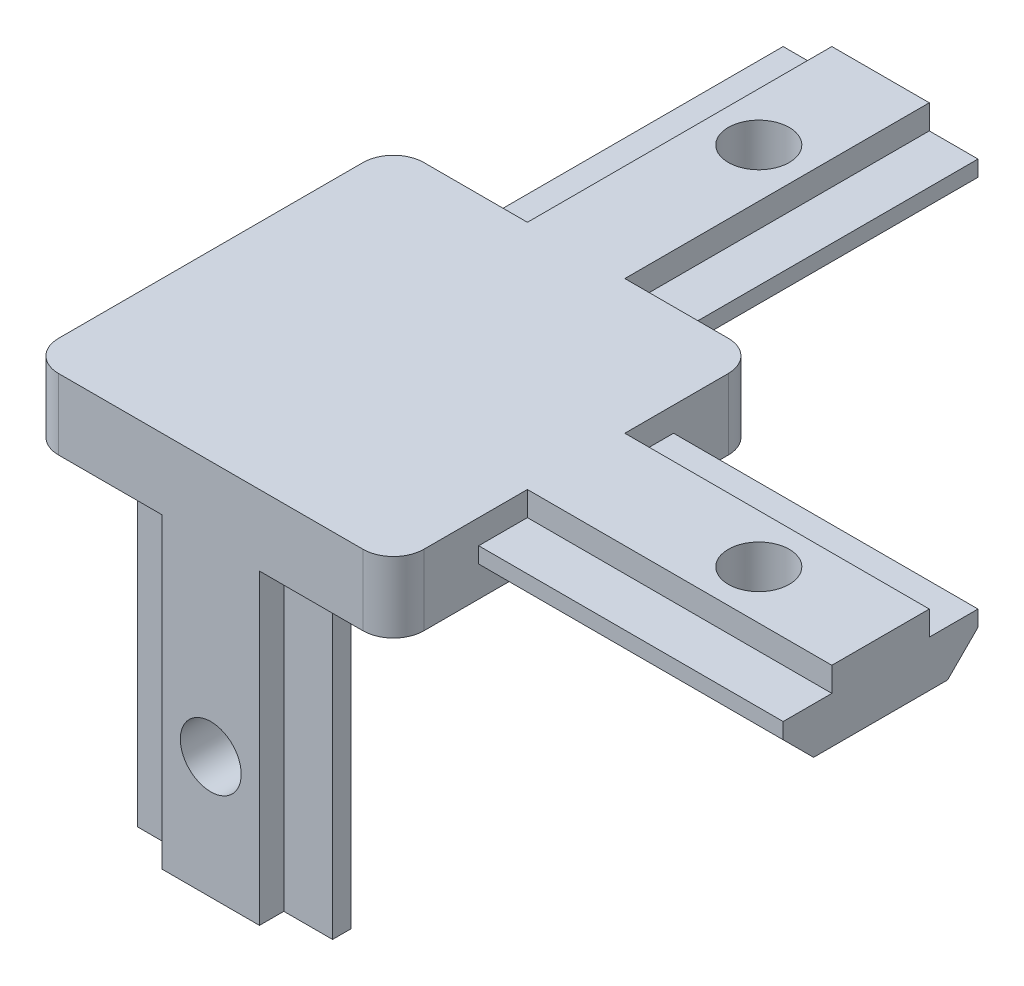
SolidWorks part; units mm, degrees
material "6063-T5"
ref_plane "前视基准面" through (0, 0, 0) normal (0, 0, 1) x (1, 0, 0)
ref_plane "上视基准面" through (0, 0, 0) normal (0, 1, 0) x (1, 0, 0)
ref_plane "右视基准面" through (0, 0, 0) normal (1, 0, 0) x (0, 0, -1)
sketch "草图1" plane through (0, 0, 0) normal (0, 1, 0) x (1, 0, 0)
  line L1 (-15, 15) -> (15, 15)
  line L2 (-15, 15) -> (-15, -15)
  line L3 (-15, -15) -> (15, -15)
  line L4 (15, 15) -> (15, -15)
  line L5 (-15, 15) -> (15, -15) construction
  line L6 (-15, -15) -> (15, 15) construction
  point P0 (0, 0)
  dimension "D1" = 30
  dimension "D2" = 30
extrude "凸台-拉伸1" add sketch "草图1" along normal blind 5.8
sketch "草图2" plane through (0, 0, 0) normal (0, -1, 0) x (-1, 0, 0)
  line L0 (0, 0) -> (0, -15) construction
  line L1 (15, -15) -> (-15, -15) construction
  line L2 (4, -15) -> (4, -13)
  line L3 (4, -13) -> (8, -13)
  line L4 (8, -13) -> (8, -11.5)
  line L5 (5.5, -9) -> (-5.5, -9)
  line L6 (8, -11.5) -> (5.5, -9)
  line L7 (4, -15) -> (-4, -15)
  line L8 (-8, -11.5) -> (-5.5, -9)
  line L9 (-8, -13) -> (-8, -11.5)
  line L10 (-4, -13) -> (-8, -13)
  line L11 (-4, -15) -> (-4, -13)
  line L12 (0, 0) -> (15, -15) construction
  line L13 (15, 4) -> (13, 4)
  line L14 (13, 4) -> (13, 8)
  line L15 (13, 8) -> (11.5, 8)
  line L16 (11.5, 8) -> (9, 5.5)
  line L17 (15, -4) -> (15, 4)
  line L18 (11.5, -8) -> (9, -5.5)
  line L19 (9, -5.5) -> (9, 5.5)
  line L20 (13, -8) -> (11.5, -8)
  line L21 (13, -4) -> (13, -8)
  line L22 (15, -4) -> (13, -4)
  point P7 (8, -9)
  point P14 (0, -9)
  point P17 (-8, -9)
  point P30 (9, 8)
  point P31 (9, 0)
  point P32 (9, -8)
  dimension "D1" = 4
  dimension "D2" = 8
  dimension "D3" = 2
  dimension "D4" = 6
extrude "凸台-拉伸2" add sketch "草图2" along normal blind 25.2
sketch "草图3" plane through (0, 0, 0) normal (0, -1, 0) x (1, 0, 0)
  line L1 (-9, -9) -> (9, -9)
  line L2 (-9, -9) -> (-9, 9)
  line L3 (-9, 9) -> (9, 9)
  line L4 (9, -9) -> (9, 9)
  line L5 (-9, -9) -> (9, 9) construction
  line L6 (-9, 9) -> (9, -9) construction
  point P0 (0, 0)
  dimension "D1" = 18
  dimension "D2" = 18
extrude "切除-拉伸1" cut sketch "草图3" against normal blind 1
sketch "草图5" plane through (0, 0, -15) normal (0, 0, -1) x (-1, 0, 0)
  line L0 (-5.5, 0) -> (5.5, 0)
  line L1 (-15, 0) -> (15, 0) construction
  line L2 (8, 2.5) -> (8, 3.8)
  line L3 (8, 3.8) -> (4, 3.8)
  line L4 (4, 3.8) -> (4, 5.8)
  line L5 (-15, 5.8) -> (15, 5.8) construction
  line L6 (4, 5.8) -> (-4, 5.8)
  line L8 (0, 0) -> (0, 5.8) construction
  line L10 (5.5, 0) -> (8, 2.5)
  line L11 (-5.5, 0) -> (-8, 2.5)
  line L12 (-4, 3.8) -> (-4, 5.8)
  line L13 (-8, 3.8) -> (-4, 3.8)
  line L14 (-8, 2.5) -> (-8, 3.8)
  point P1 (8, 0)
  point P17 (-8, 0)
  dimension "D1" = 2
  dimension "D2" = 4
  dimension "D3" = 8
extrude "凸台-拉伸4" add sketch "草图5" along normal blind 25
sketch "草图7" plane through (0, 0, 0) normal (0, 0, 1) x (1, 0, 0)
  line L0 (0, 0) -> (0, -19.2771) construction
pattern_circular "阵列(圆周)1" count 2 every 90 about axis through (0, 0, 0) along (0, -1, 0) of "凸台-拉伸4"
sketch "草图8" plane through (0, 0, 0) normal (0, -1, 0) x (-1, 0, 0)
  line L0 (-40, -5.5) -> (-40, 5.5) construction
  line L1 (-5.5, 40) -> (5.5, 40) construction
  circle A0 centre (-30, 0) radius 3
  circle A1 centre (0, 30) radius 3
  dimension "D1" = 10
  dimension "D2" = 6
  dimension "D3" = 6
  dimension "D4" = 10
sketch "草图9" plane through (-15, 0, 0) normal (-1, 0, 0) x (0, 0, 1)
  line L0 (4, -25.2) -> (-4, -25.2) construction
  circle A0 centre (0, -15.2) radius 3
  dimension "D1" = 6
  dimension "D2" = 10
sketch "草图10" plane through (0, 0, 15) normal (0, 0, 1) x (1, 0, 0)
  line L0 (4, -25.2) -> (-4, -25.2) construction
  circle A0 centre (0, -15.2) radius 3
  dimension "D1" = 6
  dimension "D2" = 10
hole_wizard "M6 螺纹孔1" positions "草图11" profile "草图12" tap size "M6" standard "GB" end condition through all
sketch "草图11" plane through (0, 0, 0) normal (0, -1, 0) x (-1, 0, 0)
  point P0 (-30, 0)
  point P4 (0, 30)
sketch "草图12" plane through (30, 0, 0) normal (1, 0, 0) x (0, 0, -1)
  line L0 (0, 0) -> (0, 5.8)
  line L1 (0, 5.8) -> (2.5, 5.8)
  line L2 (2.5, 5.8) -> (2.5, 0)
  line L5 (2.5, 0) -> (0, 0)
  line L11 (0, -6.35) -> (0, 107.95) construction
  dimension "通孔螺纹孔钻头直径" = 5
  dimension "通孔螺纹孔钻头深度" = 5.8
cosmetic thread "孔螺蚊线1" parameters "D2"=6
cosmetic thread "孔螺蚊线2" parameters "D2"=6
hole_wizard "M6 螺纹孔2" positions "草图13" profile "草图14" tap size "M6" standard "GB" end condition through all
sketch "草图13" plane through (-15, 0, 0) normal (-1, 0, 0) x (0, 0, 1)
  point P0 (0, -15.2)
sketch "草图14" plane through (-15, -15.2, 0) normal (0, 1, 0) x (0, 0, 1)
  line L0 (0, 0) -> (0, 55)
  line L1 (0, 55) -> (2.5, 55)
  line L2 (2.5, 55) -> (2.5, 0)
  line L5 (2.5, 0) -> (0, 0)
  line L11 (0, -6.35) -> (0, 107.95) construction
  dimension "通孔螺纹孔钻头直径" = 5
  dimension "通孔螺纹孔钻头深度" = 55
cosmetic thread "孔螺蚊线3" parameters "D2"=6
hole_wizard "M6 螺纹孔3" positions "草图15" profile "草图16" tap size "M6" standard "GB" end condition through all
sketch "草图15" plane through (0, 0, 15) normal (0, 0, 1) x (1, 0, 0)
  point P0 (0, -15.2)
sketch "草图16" plane through (0, -15.2, 15) normal (1, 0, 0) x (0, -1, 0)
  line L0 (0, 0) -> (0, 55)
  line L1 (0, 55) -> (2.5, 55)
  line L2 (2.5, 55) -> (2.5, 0)
  line L5 (2.5, 0) -> (0, 0)
  line L11 (0, -6.35) -> (0, 107.95) construction
  dimension "通孔螺纹孔钻头直径" = 5
  dimension "通孔螺纹孔钻头深度" = 55
cosmetic thread "孔螺蚊线4" parameters "D2"=6
fillet "圆角1" radius 2.5 4 edges at (15, 2.9, 15) (15, 2.9, -15) (-15, 2.9, -15) (-15, 2.9, 15)
